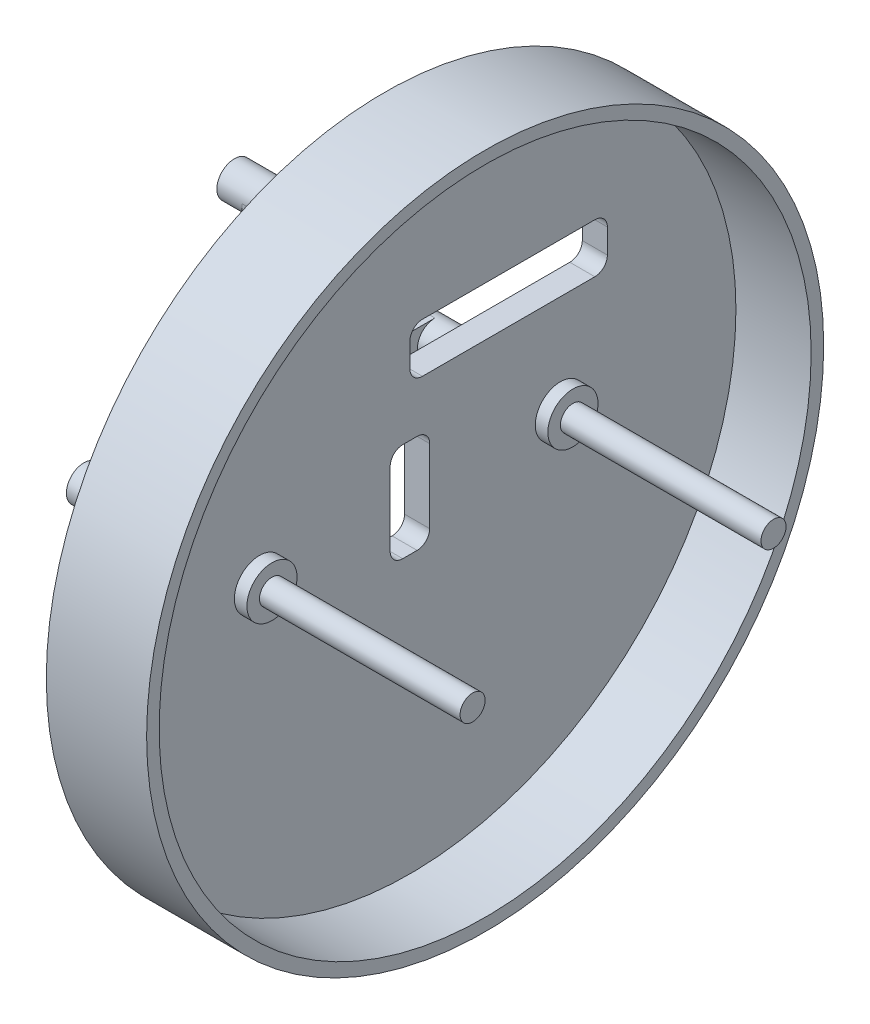
SolidWorks part; units mm, degrees
ref_plane "Front Plane" through (0, 0, 0) normal (0, 0, 1) x (1, 0, 0)
ref_plane "Top Plane" through (0, 0, 0) normal (0, 1, 0) x (1, 0, 0)
ref_plane "Right Plane" through (0, 0, 0) normal (1, 0, 0) x (0, 0, -1)
sketch "Sketch2" plane through (0, 0, 0) normal (1, 0, 0) x (0, 0, -1)
  line L0 (0, -1.778) -> (30.48, -1.778)
  line L1 (0, 1.778) -> (30.48, 1.778)
  arc A0 (0, 1.778) -> (0, -1.778) centre (0, 0) ccw
  arc A1 (30.48, -1.778) -> (30.48, 1.778) centre (30.48, 0) ccw
  dimension "D1" = 3.556
  dimension "D2" = 3.556
  dimension "D3" = 30.48
extrude "Boss-Extrude1" add sketch "Sketch2" along normal blind 2.54
sketch "Sketch3" plane through (0, 0, 0) normal (-1, 0, 0) x (0, 0, 1)
  circle A0 centre (-30.48, 0) radius 1.778
  circle A1 centre (0, 0) radius 1.778
extrude "Boss-Extrude2" add sketch "Sketch3" along normal blind 2.54 and the other way blind 12.7
ref_plane "Plane4" through (12.7, 0, 0) normal (1, 0, 0) x (0, 0, -1)
sketch "Sketch4" plane through (12.7, 0, 0) normal (1, 0, 0) x (0, 0, -1)
  line L0 (30.48, 0) -> (0, 0) construction
  circle A0 centre (15.24, 0) radius 34.29
  point P2 (30.48, 0)
  point P4 (0, 0)
  point P10 (15.24, 0)
  dimension "D1" = 68.58
extrude "Boss-Extrude3" add sketch "Sketch4" along normal blind 10.16
sketch "Sketch5" plane through (0, 0, 0) normal (1, 0, 0) x (0, 0, -1)
  line L0 (30.48, 1.778) -> (0, 1.778) construction
  line L1 (0, -1.778) -> (30.48, -1.778) construction
  line L2 (13.462, -19.05) -> (13.462, 19.05)
  line L3 (17.018, 19.05) -> (17.018, -19.05)
  arc A0 (13.462, -19.05) -> (17.018, -19.05) centre (15.24, -19.05) ccw
  arc A1 (17.018, 19.05) -> (13.462, 19.05) centre (15.24, 19.05) ccw
  point P6 (15.24, 1.778)
  dimension "D1" = 3.556
  dimension "D2" = 3.556
  dimension "D3" = 38.1
  dimension "D4" = 17.272
  dimension "D5" = 17.272
extrude "Boss-Extrude4" add sketch "Sketch5" along normal blind 2.54
sketch "Sketch6" plane through (2.54, 0, 0) normal (1, 0, 0) x (0, 0, -1)
  circle A0 centre (15.24, -19.05) radius 1.778
  circle A1 centre (15.24, 19.05) radius 1.778
extrude "Boss-Extrude5" add sketch "Sketch6" along normal up to surface (10.16 mm away) and the other way blind 5.08 up to face at (12.7, 0, -28.702)
sketch "Sketch7" plane through (22.86, 0, 0) normal (1, 0, 0) x (0, 0, -1)
  circle A0 centre (15.24, 0) radius 33.02
  circle A1 centre (15.24, 0) radius 34.29 construction
  dimension "D1" = 66.04
extrude "Cut-Extrude1" cut sketch "Sketch7" against normal blind 7.62
sketch "Sketch9" plane through (15.24, 0, 0) normal (1, 0, 0) x (0, 0, -1)
  circle A0 centre (0, 0) radius 2.54
  circle A1 centre (30.48, 0) radius 2.54
  circle A3 centre (0, 0) radius 1.778 construction
  circle A4 centre (30.48, 0) radius 1.778 construction
  dimension "D1" = 5.08
  dimension "D2" = 5.08
extrude "Boss-Extrude6" add sketch "Sketch9" along normal blind 1.27
sketch "Sketch10" plane through (16.51, 0, 0) normal (1, 0, 0) x (0, 0, -1)
  circle A0 centre (30.48, 0) radius 1.27
  circle A1 centre (0, 0) radius 1.27
  circle A2 centre (0, 0) radius 2.54 construction
  circle A3 centre (30.48, 0) radius 2.54 construction
  dimension "D1" = 2.54
  dimension "D2" = 2.54
extrude "Boss-Extrude7" add sketch "Sketch10" along normal blind 20.32
sketch "Sketch11" plane through (15.24, 0, 0) normal (1, 0, 0) x (0, 0, -1)
  line L0 (30.48, 0) -> (0, 0) construction
  line L2 (14.51, 5) -> (15.97, 5)
  line L3 (13.24, 3.73) -> (13.24, -3.73)
  line L4 (14.51, -5) -> (15.97, -5)
  line L5 (17.24, 3.73) -> (17.24, -3.73)
  line L6 (13.24, 5) -> (17.24, -5) construction
  line L7 (13.24, -5) -> (17.24, 5) construction
  arc A0 (15.97, -5) -> (17.24, -3.73) centre (15.97, -3.73) ccw
  arc A1 (13.24, -3.73) -> (14.51, -5) centre (14.51, -3.73) ccw
  arc A2 (14.51, 5) -> (13.24, 3.73) centre (14.51, 3.73) ccw
  arc A3 (15.97, 5) -> (17.24, 3.73) centre (15.97, 3.73) cw
  point P4 (15.24, 0)
  dimension "D3" = 1.27
  dimension "D1" = 10
  dimension "D2" = 4
extrude "Cut-Extrude2" cut sketch "Sketch11" against normal up to next
sketch "Sketch15" plane through (15.24, 0, 0) normal (1, 0, 0) x (0, 0, -1)
  line L0 (15.24, -29.9131) -> (15.24, 19.9131) construction
  line L1 (14.51, -5) -> (15.97, -5) construction
  line L3 (15.97, 5) -> (14.51, 5) construction
  line L7 (17.24, -3.73) -> (17.24, 3.73) construction
  line L8 (16.51, 10) -> (33.97, 10)
  line L9 (15.24, 11.27) -> (15.24, 13.73)
  line L10 (16.51, 15) -> (33.97, 15)
  line L11 (35.24, 11.27) -> (35.24, 13.73)
  arc A0 (33.97, 15) -> (35.24, 13.73) centre (33.97, 13.73) cw
  arc A1 (33.97, 10) -> (35.24, 11.27) centre (33.97, 11.27) ccw
  arc A2 (16.51, 10) -> (15.24, 11.27) centre (16.51, 11.27) cw
  arc A3 (15.24, 13.73) -> (16.51, 15) centre (16.51, 13.73) cw
  point P2 (15.24, -5)
  point P7 (15.24, 5)
  point P14 (17.24, 0)
  point P19 (35.24, 10)
  point P22 (15.24, 10)
  point P25 (15.24, 15)
  dimension "D4" = 1.27
  dimension "D1" = 5
  dimension "D2" = 20
  dimension "D3" = 10
extrude "Cut-Extrude3" cut sketch "Sketch15" against normal up to next
